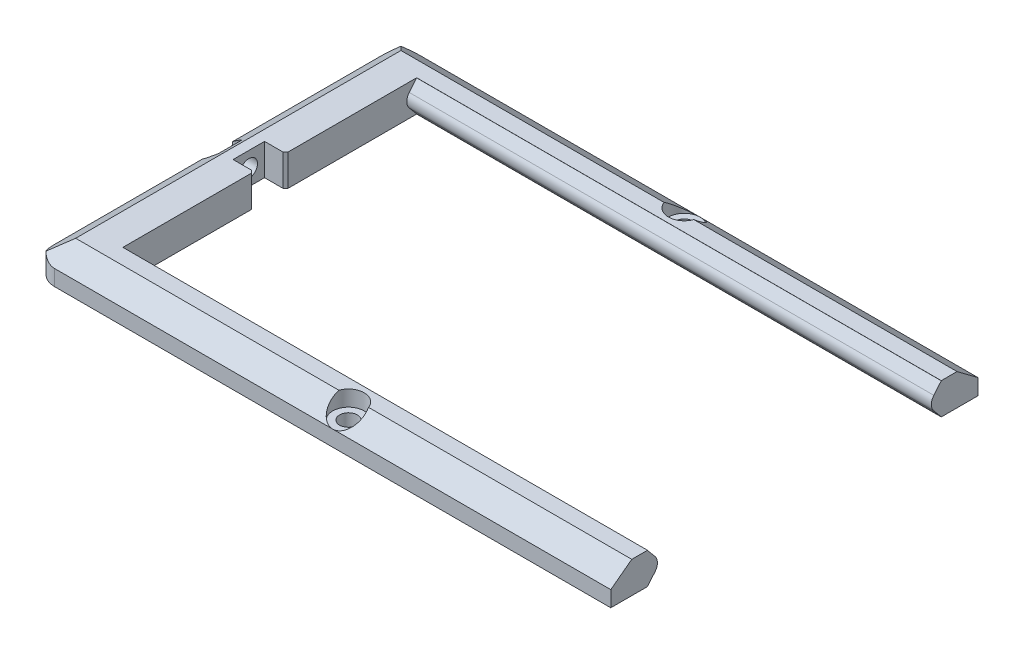
SolidWorks part; units mm, degrees
ref_plane "Płaszczyzna przednia" through (0, 0, 0) normal (0, 0, 1) x (1, 0, 0)
ref_plane "Płaszczyzna górna" through (0, 0, 0) normal (0, 1, 0) x (1, 0, 0)
ref_plane "Płaszczyzna prawa" through (0, 0, 0) normal (1, 0, 0) x (0, 0, -1)
sketch "Szkic2" plane through (0, 0, 0) normal (0, 1, 0) x (1, 0, 0)
  line L1 (55, 35) -> (-55, 35)
  line L2 (55, 35) -> (55, -35)
  line L3 (55, -35) -> (-55, -35)
  line L4 (-55, 35) -> (-55, -35)
  line L5 (55, 35) -> (-55, -35) construction
  line L6 (55, -35) -> (-55, 35) construction
  point P0 (0, 0)
  dimension "D1" = 70
  dimension "D2" = 110
extrude "Dodanie-wyciągnięcie1" add sketch "Szkic2" along normal blind 6
sketch "Szkic3" plane through (0, 6, 0) normal (0, 1, 0) x (1, 0, 0)
  line L0 (-45, 28) -> (55, 28)
  line L1 (-45, 28) -> (-45, -28)
  line L2 (55, 28) -> (55, -28)
  line L3 (-45, -28) -> (55, -28)
  line L4 (-45, 28) -> (55, -28) construction
  line L5 (55, 28) -> (-45, -28) construction
  line L6 (55, -35) -> (55, 35) construction
  point P1 (5, 0)
  point P3 (55, 0)
  point P8 (55, 0)
  dimension "D1" = 56
  dimension "D2" = 100
extrude "Wytnij-wyciągnięcie1" cut sketch "Szkic3" against normal through all
sketch "Szkic4" plane through (0, 6, 0) normal (0, 1, 0) x (1, 0, 0)
  line L0 (2, 32) -> (2, -32) construction
  line L1 (0, 0) -> (2, 0) construction
  circle A0 centre (2, 32) radius 1.7
  circle A1 centre (2, -32) radius 1.7
  point P4 (0, 0)
  dimension "D2" = 3.4
  dimension "D3" = 3.4
  dimension "D1" = 64
  dimension "D4" = 2
extrude "Wytnij-wyciągnięcie2" cut sketch "Szkic4" against normal through all
sketch "Szkic5" plane through (55, 0, 0) normal (1, 0, 0) x (0, 0, -1)
  line L0 (-28, 0) -> (-28, 5.9794) construction
  line L1 (-28, 0) -> (-28, 6) construction
  line L2 (-28, 5.9794) -> (-25.5, 3)
  line L3 (-25.5, 3) -> (-28, 0.0206)
  line L4 (-28, 0.0206) -> (-28, 5.9794)
  point P9 (-28, 3)
  point P10 (-28, 3)
  dimension "D1" = 40
  dimension "D2" = 40
  dimension "D3" = 2.5
extrude "Dodanie-wyciągnięcie2" add sketch "Szkic5" against normal up to surface (100 mm away) up to face at (-45, 3, 0)
fillet "Zaokrąglenie3" radius 2 1 edges at (5, 3, 25.5)
mirror "Lustro2" about plane through (0, 0, 0) normal (0, 0, 1) of "Dodanie-wyciągnięcie2", "Zaokrąglenie3"
sketch "Szkic6" plane through (-55, 0, 0) normal (-1, 0, 0) x (0, 0, 1)
  line L0 (-3, 6) -> (-3, 0)
  line L1 (-3, 6) -> (3, 6)
  line L2 (-3, 0) -> (3, 0)
  line L3 (3, 6) -> (3, 0)
  line L4 (-3, 6) -> (3, 0) construction
  line L5 (-3, 0) -> (3, 6) construction
  point P0 (0, 0)
  point P1 (0, 3)
  dimension "D1" = 6
  dimension "D2" = 6
extrude "Wytnij-wyciągnięcie5" cut sketch "Szkic6" against normal blind 4 from offset 6 offset against normal yes
sketch "Szkic7" plane through (-49, 0, 0) normal (1, 0, 0) x (0, 0, -1)
  line L0 (0, 6) -> (0, 0) construction
  line L2 (3, 0) -> (-3, 0) construction
  line L3 (-3, 6) -> (3, 6) construction
  circle A0 centre (0, 3) radius 1.65
  dimension "D1" = 3.3
extrude "Wytnij-wyciągnięcie6" cut sketch "Szkic7" against normal through all
sketch "Szkic8" plane through (0, 6, 0) normal (0, 1, 0) x (1, 0, 0)
  circle A0 centre (2, -32) radius 3
  circle A1 centre (2, 32) radius 3
  dimension "D1" = 6
  dimension "D2" = 6
sketch "Szkic9" plane through (-55, 0, 0) normal (-1, 0, 0) x (0, 0, 1)
  circle A0 centre (0, 3) radius 2.9
  dimension "D1" = 5.8
chamfer "Sfazowanie1" distance 3 distance2 4 3 edges at (0, 6, 35) (-55, 6, 0) (0, 6, -35) first distance on face at (0, 3, 35) first distance on face at (-55, 3, -1.65) first distance on face at (0, 3, -35)
extrude "Wytnij-wyciągnięcie8" cut sketch "Szkic8" against normal blind 3
fillet "Zaokrąglenie2" radius 4 2 edges at (-55, 1.5, 35) (-55, 1.5, -35)
extrude "Wytnij-wyciągnięcie9" cut sketch "Szkic9" against normal blind 2.5 contours A0
chamfer "Sfazowanie2" distance 0.5 angle 45 2 edges at (-45, 3, -3) (-45, 3, 3)
